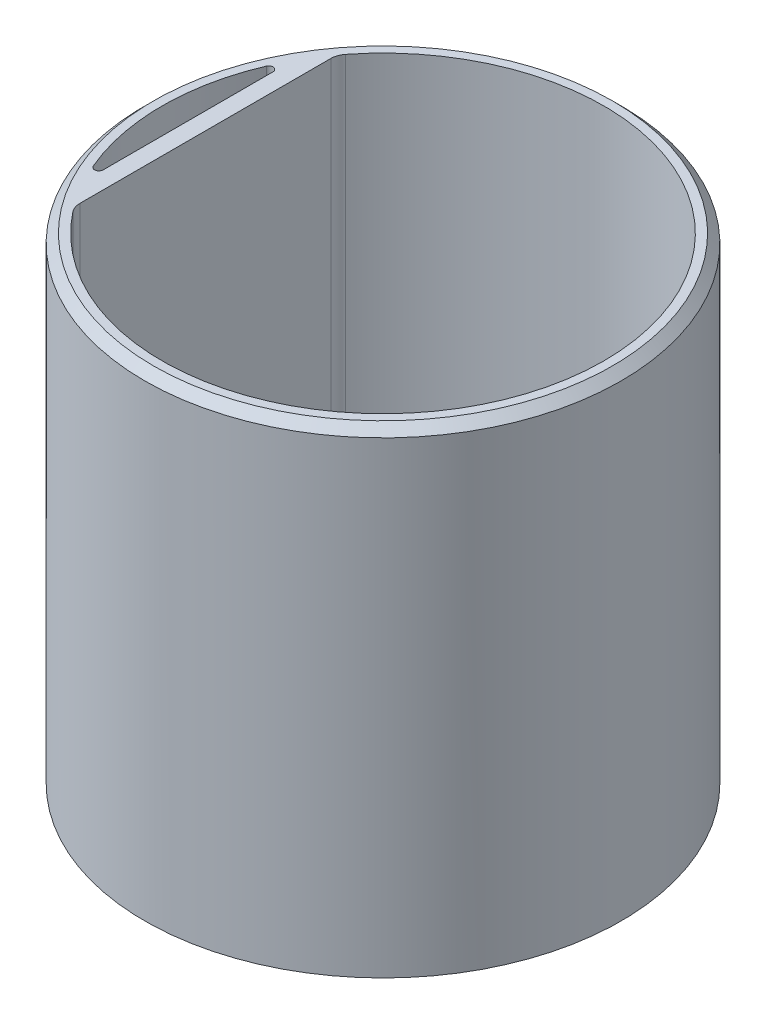
SolidWorks part; units mm, degrees
ref_plane "Front Plane" through (0, 0, 0) normal (0, 0, 1) x (1, 0, 0)
ref_plane "Top Plane" through (0, 0, 0) normal (0, 1, 0) x (1, 0, 0)
ref_plane "Right Plane" through (0, 0, 0) normal (1, 0, 0) x (0, 0, -1)
sketch "Sketch1" plane through (0, 0, 0) normal (0, 1, 0) x (1, 0, 0)
  line L0 (-25.5, 0) -> (-22.5, 0) construction
  line L1 (-22.5, -12) -> (-22.5, 12) construction
  line L2 (-22.5, 0) -> (-20.5, 0) construction
  line L3 (-20.5, -15.1658) -> (-20.5, 15.1658) construction
  line L4 (-20.5, 15.1658) -> (-20.5, -15.1658)
  line L5 (-22.5, 12) -> (-22.5, -12)
  circle A0 centre (0, 0) radius 27.5
  circle A1 centre (0, 0) radius 25.5 construction
  arc A2 (-20.5, 15.1658) -> (-20.5, -15.1658) centre (0, 0) cw
  arc A3 (-22.5, -12) -> (-22.5, 12) centre (0, 0) cw
  point P9 (-22.5, 0)
  point P13 (-20.5, 0)
  dimension "D1" = 55
  dimension "D2" = 51
  dimension "D3" = 3
  dimension "D4" = 2
extrude "Boss-Extrude1" add sketch "Sketch1" along normal blind 55 contours A0 L4 A2 L5 A3 region at (-26.7222, 0, 0)
chamfer "Chamfer1" distance 1 angle 45 1 edges at (0, 55, 27.5)
fillet "Fillet2" radius 0.5 2 edges at (-22.5, 27.5, -12) (-22.5, 27.5, 12)
fillet "Fillet3" radius 2 2 edges at (-20.5, 27.5, -15.1658) (-20.5, 27.5, 15.1658)
ref_plane "Plane1" through (0, 50.95, 0) normal (0, 1, 0) x (1, 0, 0)
sketch "Sketch3" plane through (0, 50.95, 0) normal (0, 1, 0) x (1, 0, 0)
  line L1 (-31.0531, -2.25) -> (-23.9469, -2.25)
  line L2 (-31.0531, -2.25) -> (-31.0531, 2.25)
  line L3 (-31.0531, 2.25) -> (-23.9469, 2.25)
  line L4 (-23.9469, -2.25) -> (-23.9469, 2.25)
  line L5 (-31.0531, -2.25) -> (-23.9469, 2.25) construction
  line L6 (-31.0531, 2.25) -> (-23.9469, -2.25) construction
  circle A0 centre (0, 0) radius 27.5 construction
  point P0 (-27.5, 0)
  dimension "D1" = 4.5
extrude "Cut-Extrude2" cut sketch "Sketch3" against normal blind 4.5
fillet "Fillet6" radius 1 4 edges at (-27.4078, 48.7, -2.25) (-27.5, 46.45, 0) (-27.4078, 48.7, 2.25) (-27.5, 50.95, 0)
fillet "Fillet7" radius 1 4 edges at (-25.4005, 48.7, 2.25) (-25.5, 46.45, 0) (-25.4005, 48.7, -2.25) (-25.5, 50.95, 0)
fillet "Fillet8" radius 1 12 edges at (-25.7944, 51.1466, 2.3872) (-25.7944, 51.1466, -2.3872) (-25.7944, 46.2534, -2.3872) (-25.7944, 46.2534, 2.3872) (-26.8807, 51.0788, 2.4359) (-26.8807, 51.0788, -2.4359) (-26.8807, 46.3212, -2.4359) (-26.8807, 46.3212, 2.4359)
fillet "Fillet14" radius 2 4 edges at (-22.9, 0, 10.2879) (-22.5, 0, 0) (-22.9, 0, -10.2879) (-25.5, 0, 0)
